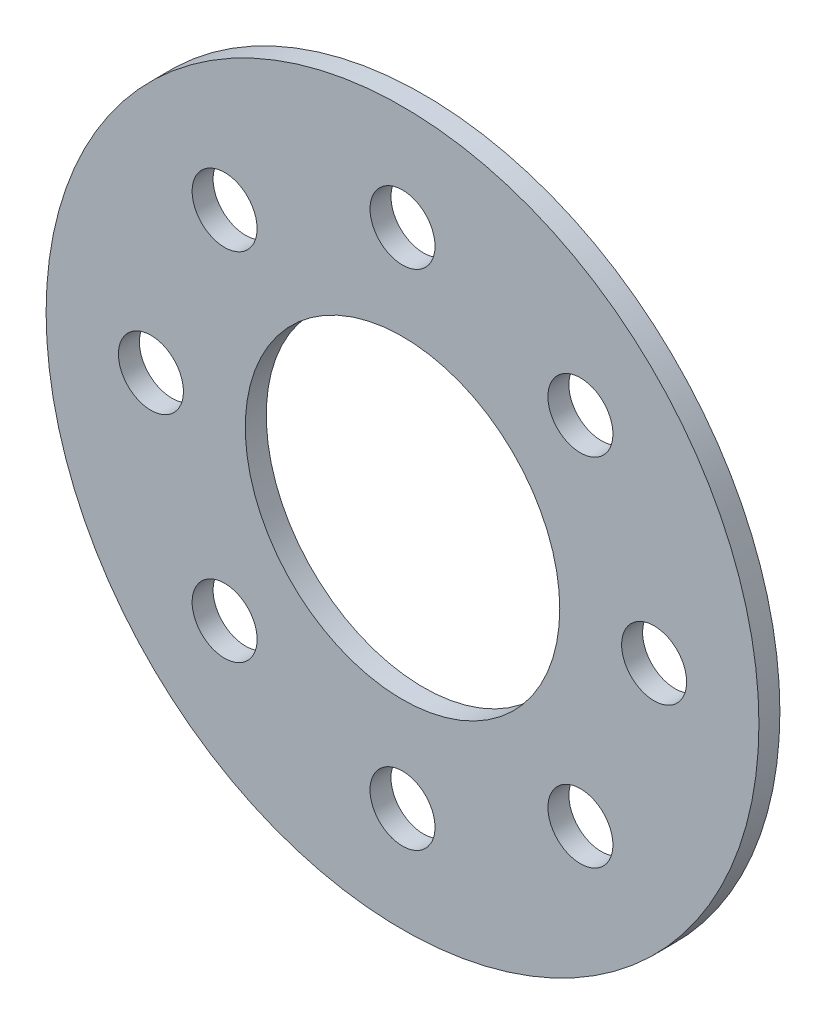
SolidWorks part; units mm, degrees
material "PLA 50%"
ref_plane "Front Plane" through (0, 0, 0) normal (0, 0, 1) x (1, 0, 0)
ref_plane "Top Plane" through (0, 0, 0) normal (0, 1, 0) x (1, 0, 0)
ref_plane "Right Plane" through (0, 0, 0) normal (1, 0, 0) x (0, 0, -1)
ref_axis "X" through (-88.99, 0, 0) along (1, 0, 0)
ref_axis "Y" through (0, 55, 0) along (0, -1, 0)
ref_axis "Z" through (0, 0, -88.99) along (0, 0, 1)
sketch "Sketch1" plane through (0, 0, 0) normal (0, 0, 1) x (1, 0, 0)
  circle A0 centre (0, 0) radius 7.5
  circle A1 centre (0, 0) radius 17
  dimension "D1" = 34
  dimension "D2" = 15
extrude "Boss-Extrude1" add sketch "Sketch1" along normal blind 1
sketch "Sketch2" plane through (0, 0, 1) normal (0, 0, 1) x (1, 0, 0)
  circle A0 centre (0, 12) radius 1.55
  dimension "D1" = 3.1
  dimension "D2" = 12
extrude "Cut-Extrude1" cut sketch "Sketch2" against normal through all both
pattern_circular "CirPattern1" count 8 over 360 about axis through (0, 0, 1) along (0, 0, -1) of "Cut-Extrude1"
